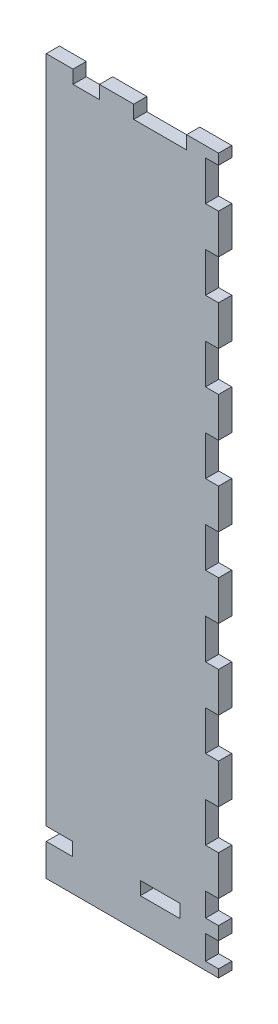
SolidWorks part; units mm, degrees
material "Balsa"
ref_plane "Plan de face" through (0, 0, 0) normal (0, 0, 1) x (1, 0, 0)
ref_plane "Plan de dessus" through (0, 0, 0) normal (0, 1, 0) x (1, 0, 0)
ref_plane "Plan de droite" through (0, 0, 0) normal (1, 0, 0) x (0, 0, -1)
sketch "Esquisse1" plane through (0, 0, 0) normal (0, 0, 1) x (1, 0, 0)
  line L1 (65.1211, 0) -> (0, 0)
  line L2 (65.1211, 0) -> (65.1211, 270)
  line L3 (65.1211, 270) -> (0, 270)
  line L4 (0, 0) -> (0, 270)
  dimension "D1" = 270
  dimension "D2" = 65.1211
extrude "Boss.-Extru.1" add sketch "Esquisse1" against normal blind 5
sketch "Esquisse2" plane through (0, 0, 0) normal (0, 0, 1) x (1, 0, 0)
  line L0 (0, 270) -> (0, 0) construction
  line L1 (0, 17.15) -> (10, 17.15)
  line L2 (0, 17.15) -> (0, 12.15)
  line L3 (0, 12.15) -> (10, 12.15)
  line L4 (10, 17.15) -> (10, 12.15)
  line L5 (65.1211, 0) -> (65.1211, 270) construction
  line L6 (50.5493, 17.15) -> (35.5493, 17.15)
  line L7 (50.5493, 17.15) -> (50.5493, 12.15)
  line L8 (50.5493, 12.15) -> (35.5493, 12.15)
  line L9 (35.5493, 17.15) -> (35.5493, 12.15)
  line L10 (65.1211, 12.15) -> (60.2011, 12.15)
  line L11 (65.1211, 12.15) -> (65.1211, 3)
  line L12 (65.1211, 3) -> (60.2011, 3)
  line L13 (60.2011, 12.15) -> (60.2011, 3)
  line L14 (0, 0) -> (65.1211, 0) construction
  line L15 (65.1211, 0) -> (65.1211, 270) construction
  line L16 (65.1211, 17.15) -> (60.2011, 17.15)
  line L17 (65.1211, 17.15) -> (65.1211, 26)
  line L18 (65.1211, 26) -> (60.2011, 26)
  line L19 (60.2011, 17.15) -> (60.2011, 26)
  line L20 (65.1211, 270) -> (0, 270) construction
  line L21 (65.1211, 266) -> (60.2011, 266)
  line L22 (65.1211, 266) -> (65.1211, 251)
  line L23 (65.1211, 251) -> (60.2011, 251)
  line L24 (60.2011, 266) -> (60.2011, 251)
  line L25 (65.1211, 236) -> (60.2011, 236)
  line L26 (65.1211, 236) -> (65.1211, 221)
  line L27 (65.1211, 221) -> (60.2011, 221)
  line L28 (60.2011, 236) -> (60.2011, 221)
  line L29 (65.1211, 206) -> (60.2011, 206)
  line L30 (65.1211, 206) -> (65.1211, 191)
  line L31 (65.1211, 191) -> (60.2011, 191)
  line L32 (60.2011, 206) -> (60.2011, 191)
  line L33 (65.1211, 176) -> (60.2011, 176)
  line L34 (65.1211, 176) -> (65.1211, 161)
  line L35 (65.1211, 161) -> (60.2011, 161)
  line L36 (60.2011, 176) -> (60.2011, 161)
  line L37 (65.1211, 146) -> (60.2011, 146)
  line L38 (65.1211, 146) -> (65.1211, 131)
  line L39 (65.1211, 131) -> (60.2011, 131)
  line L40 (60.2011, 146) -> (60.2011, 131)
  line L41 (65.1211, 116) -> (60.2011, 116)
  line L42 (65.1211, 116) -> (65.1211, 101)
  line L43 (65.1211, 101) -> (60.2011, 101)
  line L44 (60.2011, 116) -> (60.2011, 101)
  line L45 (65.1211, 86) -> (60.2011, 86)
  line L46 (65.1211, 86) -> (65.1211, 71)
  line L47 (65.1211, 71) -> (60.2011, 71)
  line L48 (60.2011, 86) -> (60.2011, 71)
  line L49 (65.1211, 56) -> (60.2011, 56)
  line L50 (65.1211, 56) -> (65.1211, 41)
  line L51 (65.1211, 41) -> (60.2011, 41)
  line L52 (60.2011, 56) -> (60.2011, 41)
  line L53 (65.1211, 270) -> (0, 270) construction
  line L54 (10.1211, 270) -> (20.1211, 270)
  line L55 (10.1211, 270) -> (10.1211, 265)
  line L56 (10.1211, 265) -> (20.1211, 265)
  line L57 (20.1211, 270) -> (20.1211, 265)
  line L59 (33.0493, 265) -> (53.0493, 265)
  line L60 (33.0493, 265) -> (33.0493, 270)
  line L61 (33.0493, 270) -> (53.0493, 270)
  line L62 (53.0493, 265) -> (53.0493, 270)
  dimension "D1" = 3
  dimension "D2" = 4.92
  dimension "D3" = 9.15
  dimension "D4" = 12.15
  dimension "D5" = 5
  dimension "D6" = 5
  dimension "D7" = 15
  dimension "D8" = 5
  dimension "D9" = 15
  dimension "D10" = 4
  dimension "D12" = 30
  dimension "D13" = 10
  dimension "D14" = 20
  dimension "D15" = 55
  dimension "D16" = 5
  dimension "D17" = 12.0718
  dimension "D11" = 8
extrude "Enlèv. mat.-Extru.1" cut sketch "Esquisse2" against normal blind 5
